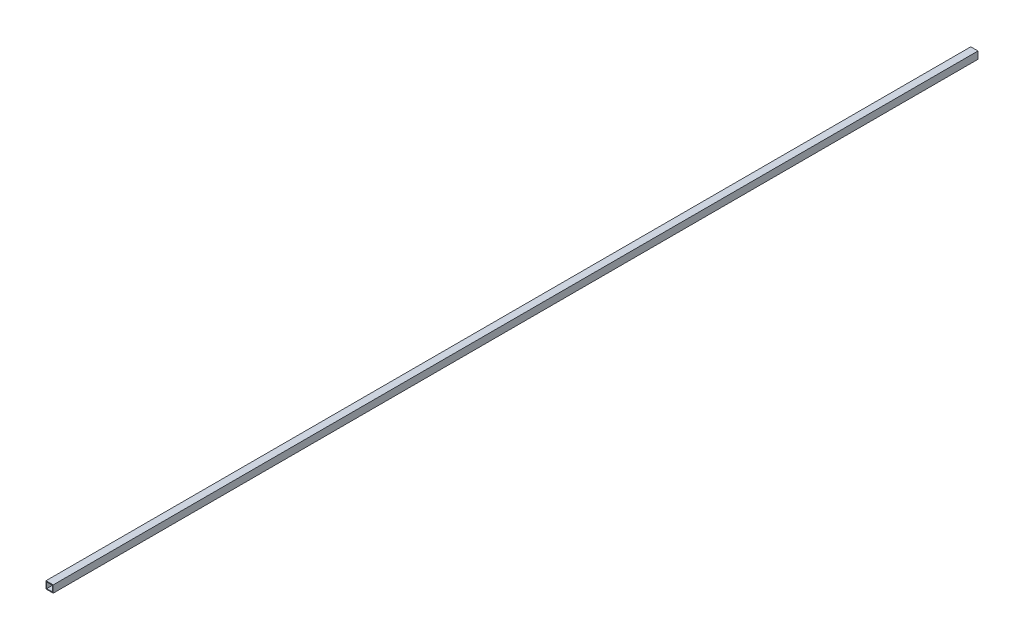
SolidWorks part; units mm, degrees
ref_plane "Front Plane" through (0, 0, 0) normal (0, 0, 1) x (1, 0, 0)
ref_plane "Top Plane" through (0, 0, 0) normal (0, 1, 0) x (1, 0, 0)
ref_plane "Right Plane" through (0, 0, 0) normal (1, 0, 0) x (0, 0, -1)
sketch "Sketch1" plane through (0, 0, 0) normal (0, 0, 1) x (1, 0, 0)
  line L1 (0, 0) -> (19.05, 0)
  line L2 (0, 0) -> (0, 19.05)
  line L3 (0, 19.05) -> (19.05, 19.05)
  line L4 (19.05, 0) -> (19.05, 19.05)
  dimension "D1" = 19.05
  dimension "D2" = 19.05
extrude "Boss-Extrude1" add sketch "Sketch1" against normal blind 2438.4
sketch "Sketch2" plane through (0, 0, 0) normal (0, 0, 1) x (1, 0, 0)
  line L0 (19.05, 0) -> (19.05, 19.05) construction
  line L1 (1.905, 17.145) -> (17.145, 17.145)
  line L2 (1.905, 17.145) -> (1.905, 1.905)
  line L3 (1.905, 1.905) -> (17.145, 1.905)
  line L4 (17.145, 17.145) -> (17.145, 1.905)
  line L5 (19.05, 19.05) -> (0, 19.05) construction
  line L6 (0, 0) -> (19.05, 0) construction
  dimension "D1" = 15.24
  dimension "D2" = 15.24
  dimension "D3" = 1.905
  dimension "D4" = 1.905
  dimension "D5" = 1.905
extrude "Cut-Extrude1" cut sketch "Sketch2" against normal through all
